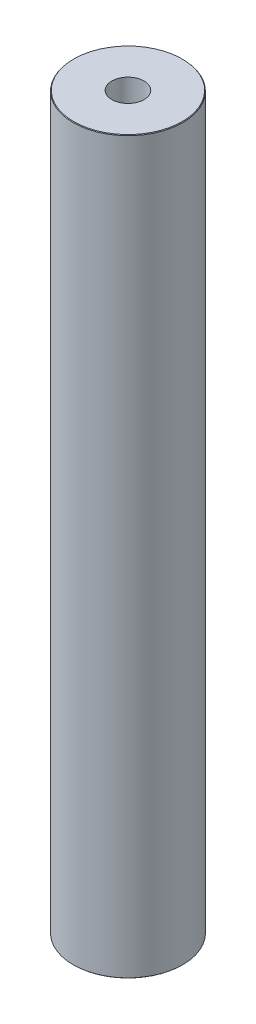
SolidWorks part; units mm, degrees
ref_plane "Front Plane" through (0, 0, 0) normal (0, 0, 1) x (1, 0, 0)
ref_plane "Top Plane" through (0, 0, 0) normal (0, 1, 0) x (1, 0, 0)
ref_plane "Right Plane" through (0, 0, 0) normal (1, 0, 0) x (0, 0, -1)
sketch "Sketch1" plane through (0, 0, 0) normal (0, 1, 0) x (1, 0, 0)
  circle A0 centre (0, 0) radius 45
  dimension "SHAFT_OD" = 90
extrude "Boss-Extrude1" add sketch "Sketch1" along normal blind 600
sketch "Sketch2" plane through (0, 0, 0) normal (0, 1, 0) x (1, 0, 0)
  circle A0 centre (0, 0) radius 13.2521
  dimension "BORE_D" = 26.5043
extrude "Cut-Extrude1" cut sketch "Sketch2" along normal through all
chamfer "Chamfer1" distance 0.5018 angle 41.483 2 edges at (0, 600, 45) (0, 0, 45) first distance on face at (0, 600, 45) first distance on face at (0, 0, 13.2521)
